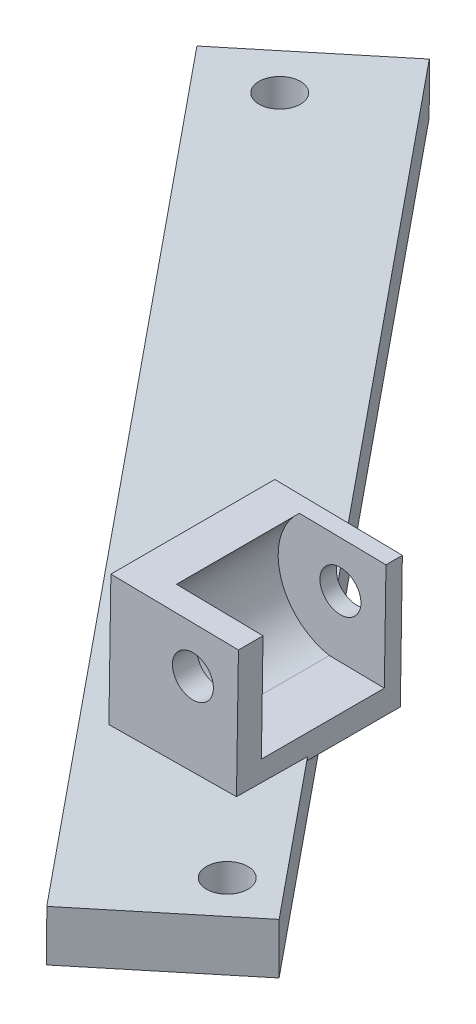
SolidWorks part; units mm, degrees
ref_plane "Front Plane" through (0, 0, 0) normal (0, 0, 1) x (1, 0, 0)
ref_plane "Top Plane" through (0, 0, 0) normal (0, 1, 0) x (1, 0, 0)
ref_plane "Right Plane" through (0, 0, 0) normal (1, 0, 0) x (0, 0, -1)
sketch "Sketch1" plane through (0, 0, 0) normal (0, 0, 1) x (1, 0, 0)
  line L0 (-620.8374, 110.7203) -> (-621.1503, 90.2249)
  line L1 (-604.7125, 110.4741) -> (-634.2525, 110.9251) construction
  line L2 (-621.1503, 90.2249) -> (-640.9147, 90.5267)
  line L3 (-640.9147, 90.5267) -> (-640.6018, 111.0221)
  line L4 (-640.6018, 111.0221) -> (-620.8374, 110.7203)
  line L5 (-606.4491, 93.8109) -> (-629.5989, 94.1643) construction
  line L6 (-606.4491, 93.8109) -> (-629.5989, 94.1643)
  arc A0 (-634.2525, 110.9251) -> (-634.4712, 96.6012) centre (-627.8931, 103.6644) ccw construction
  arc A1 (-634.4712, 96.6012) -> (-629.5989, 94.1643) centre (-627.8931, 103.6644) ccw construction
  arc A2 (-634.2525, 110.9251) -> (-634.4712, 96.6012) centre (-627.8931, 103.6644) ccw
  arc A3 (-634.4712, 96.6012) -> (-629.5989, 94.1643) centre (-627.8931, 103.6644) ccw
  dimension "D1" = 3.81
  dimension "D2" = 6.35
  dimension "D3" = 19.7667
extrude "Boss-Extrude1" add sketch "Sketch1" against normal blind 21.59 contours A3 A2 L4 L3 L2 L0 L6 region at (-621.4085, 92.1341, 0)
sketch "Sketch2" plane through (0, 0, -19.05) normal (0, 0, -1) x (-1, 0, 0)
  line L0 (621.0921, 94.0345) -> (620.8374, 110.7203)
  line L1 (604.6203, 110.4727) -> (634.2525, 110.9251) construction
  line L2 (620.8374, 110.7203) -> (634.2525, 110.9251)
  line L3 (621.0921, 94.0345) -> (629.5989, 94.1643) construction
  line L4 (621.0921, 94.0345) -> (629.5989, 94.1643)
  line L5 (621.0921, 94.0345) -> (629.5989, 94.1643)
  circle A0 centre (627.8931, 103.6644) radius 3.175 construction
  arc A1 (629.5989, 94.1643) -> (634.2525, 110.9251) centre (627.8931, 103.6644) ccw construction
  circle A2 centre (627.8931, 103.6644) radius 3.175
  arc A3 (629.5989, 94.1643) -> (634.2525, 110.9251) centre (627.8931, 103.6644) ccw
  circle M6 centre (627.8931, 103.6644) radius 3.175
  line M7 (604.4767, 96.1432) -> (634.4712, 96.6012)
  arc M8 (634.4712, 96.6012) -> (634.2525, 110.9251) centre (627.8931, 103.6644) ccw
  line M9 (634.2525, 110.9251) -> (604.6203, 110.4727)
extrude "Boss-Extrude3" add sketch "Sketch2" along normal up to surface (2.54 mm away) contours L0 M7 M8 M9 M6 | L4 A3 L0 M7 region at (-626.9307, 95.381, -19.05) region at (-621.1681, 103.5617, -19.05) up to face at (-632.1463, 98.2392, -21.59)
sketch "Sketch3" plane through (0, 0, 0) normal (0, 0, 1) x (1, 0, 0)
  line L0 (-640.6018, 111.0221) -> (-620.8374, 110.7203)
  line L1 (-620.8374, 110.7203) -> (-621.1503, 90.2249)
  line L2 (-621.1503, 90.2249) -> (-640.9147, 90.5267)
  line L3 (-640.9147, 90.5267) -> (-640.6018, 111.0221)
  circle A0 centre (-627.8931, 103.6644) radius 3.175
  dimension "D1" = 6.35
extrude "Boss-Extrude4" add sketch "Sketch3" along normal blind 3.81 contours L3 L0 L1 L2 | A0
ref_plane "Plane1" through (-1.0096, 97.2566, -1.0889) normal (-0.0104, 0.9999, -0.0112) x (0.9999, 0.0104, -0.0001)
sketch "Sketch4" plane through (-1.0096, 97.2566, -1.0889) normal (-0.0104, 0.9999, -0.0112) x (0.9999, 0.0104, -0.0001)
  line L0 (-726.1965, 95.0872) -> (-619.8166, -34.5745)
  line L5 (-619.8166, -34.5745) -> (-600.0384, -18.3477)
  line L6 (-600.0384, -18.3477) -> (-706.4183, 111.314)
  line L7 (-706.4183, 111.314) -> (-726.1965, 95.0872)
  circle A1 centre (-713.3679, 95.0872) radius 3.175
  circle A2 centre (-609.7559, -16.6729) radius 3.175
  dimension "D7" = 7.4584
  dimension "D9" = 6.35
  dimension "D10" = 6.35
  dimension "D6" = 8.137
  dimension "D2" = 0
  dimension "D3" = 180
  dimension "D4" = 90
  dimension "D5" = 9.9178
  dimension "D8" = 19.1327
  dimension "D11" = 15.6651
extrude "Boss-Extrude5" add sketch "Sketch4" against normal up to surface (7.7804 mm away)
